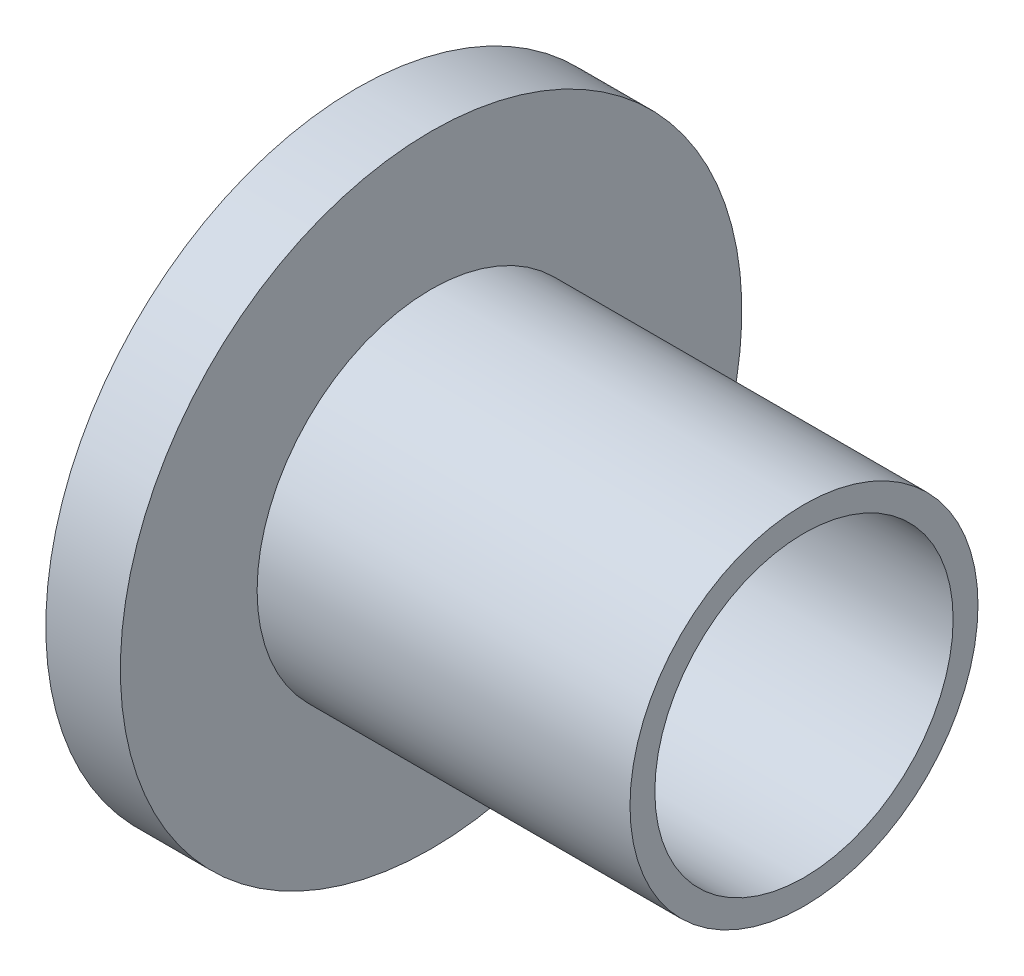
SolidWorks part; units mm, degrees
ref_plane "Front Plane" through (0, 0, 0) normal (0, 0, 1) x (1, 0, 0)
ref_plane "Top Plane" through (0, 0, 0) normal (0, 1, 0) x (1, 0, 0)
ref_plane "Right Plane" through (0, 0, 0) normal (1, 0, 0) x (0, 0, -1)
sketch "Sketch1" plane through (0, 0, 0) normal (0, 0, 1) x (1, 0, 0)
  line L0 (-64.9001, 0) -> (64.9001, 0) construction
  line L1 (-6, 25) -> (-6, 7.5)
  line L2 (-3, 10) -> (0, 10)
  line L3 (0, 10) -> (0, 12)
  line L4 (0, 12) -> (30, 12)
  line L5 (30, 12) -> (30, 14)
  line L6 (30, 14) -> (0, 14)
  line L7 (0, 14) -> (0, 25)
  line L8 (0, 25) -> (-6, 25)
  line L9 (-3, 10) -> (-3, 5.5)
  line L10 (-3, 5.5) -> (-16, 5.5)
  line L11 (-16, 5.5) -> (-16, 7.5)
  line L12 (-16, 7.5) -> (-6, 7.5)
  line L13 (-3, 10) -> (-3, 25) construction
  line L14 (-6, 10) -> (0, 10) construction
  point P3 (0, 0)
  point P6 (-3, 25)
  point P15 (-17.9013, 5.5)
  dimension "D1" = 24
  dimension "D2" = 28
  dimension "D3" = 20
  dimension "D4" = 50
  dimension "D5" = 6
  dimension "D6" = 30
  dimension "D7" = 15
  dimension "D8" = 10
  dimension "D9" = 2
revolve "Revolve1" add sketch "Sketch1" angle 360 about L0
